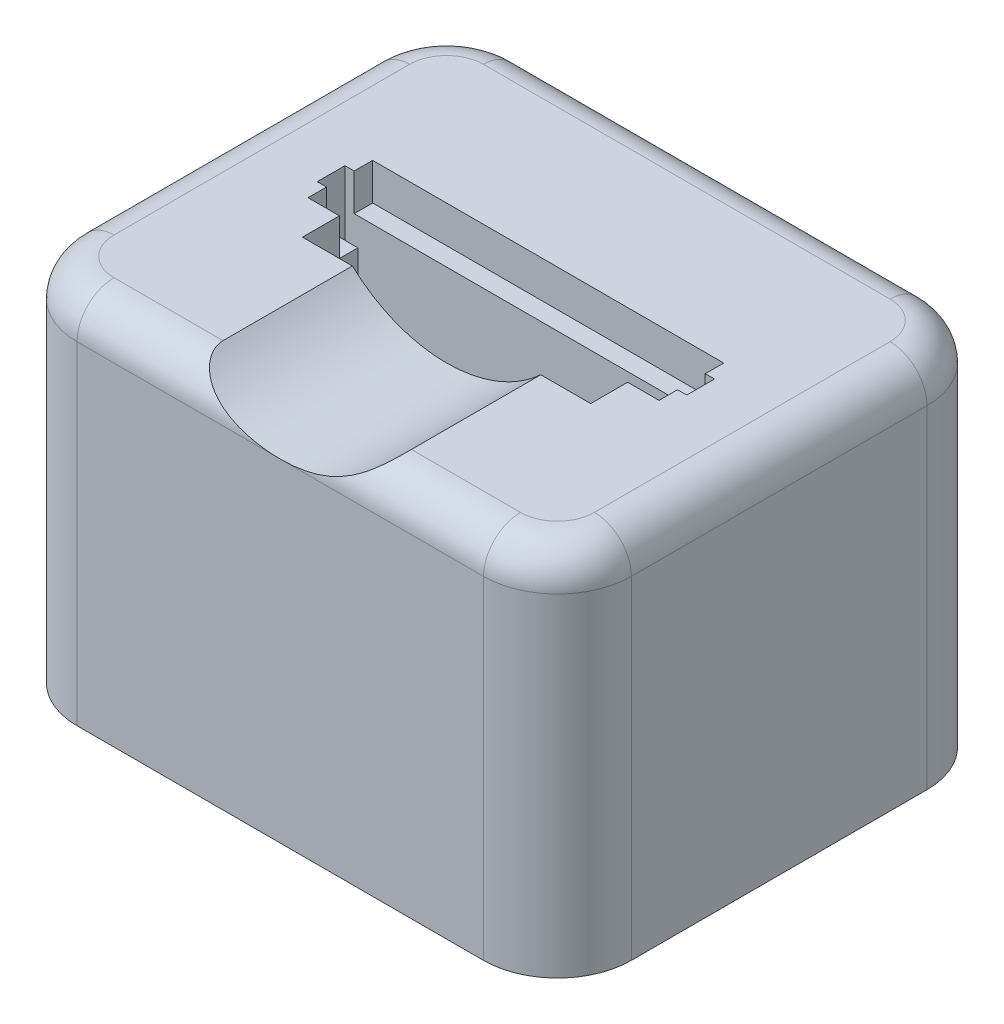
SolidWorks part; units mm, degrees
ref_plane "Спереди" through (0, 0, 0) normal (0, 0, 1) x (1, 0, 0)
ref_plane "Сверху" through (0, 0, 0) normal (0, 1, 0) x (1, 0, 0)
ref_plane "Справа" through (0, 0, 0) normal (1, 0, 0) x (0, 0, -1)
sketch "Эскиз1" plane through (0, 0, 0) normal (0, 1, 0) x (1, 0, 0)
  line L1 (4, 0) -> (26, 0)
  line L2 (0, 4) -> (0, 20)
  line L3 (4, 24) -> (26, 24)
  line L4 (30, 4) -> (30, 20)
  arc A0 (26, 24) -> (30, 20) centre (26, 20) cw
  arc A1 (26, 0) -> (30, 4) centre (26, 4) ccw
  arc A2 (4, 0) -> (0, 4) centre (4, 4) cw
  arc A3 (0, 20) -> (4, 24) centre (4, 20) cw
  point P10 (30, 0)
  point P13 (0, 0)
  point P16 (0, 24)
  dimension "D3" = 4
  dimension "D1" = 30
  dimension "D2" = 24
extrude "Бобышка-Вытянуть1" add sketch "Эскиз1" along normal blind 20
sketch "Эскиз2" plane through (0, 20, 0) normal (0, 1, 0) x (1, 0, 0)
  line L0 (0, 20) -> (0, 4) construction
  line L1 (5, 13.5) -> (25, 13.5)
  line L2 (5, 13.5) -> (5, 12)
  line L3 (5, 12) -> (25, 12)
  line L4 (25, 13.5) -> (25, 12)
  dimension "D1" = 1.5
  dimension "D2" = 20
  dimension "D3" = 5
  dimension "D4" = 12
sketch "Эскиз6" plane through (0, 0, 0) normal (0, -1, 0) x (1, 0, 0)
  circle A0 centre (4, -4) radius 0.9
  circle A1 centre (26, -4) radius 0.9
  circle A2 centre (26, -20) radius 0.9
  circle A3 centre (4, -20) radius 0.9
  dimension "D1" = 1.8
extrude "Вырез-Вытянуть5" cut sketch "Эскиз6" against normal blind 7
sketch "Эскиз3" plane through (0, 20, 0) normal (0, 1, 0) x (1, 0, 0)
  line L0 (5, 12) -> (25, 12) construction
  line L1 (7.2, 12) -> (22.8, 12)
  line L2 (7.2, 12) -> (7.2, 9)
  line L3 (7.2, 9) -> (22.8, 9)
  line L4 (22.8, 12) -> (22.8, 9)
  point P7 (15, 12)
  point P8 (15, 12)
  dimension "D1" = 15.6
  dimension "D2" = 3
extrude "Вырез-Вытянуть1" cut sketch "Эскиз3" against normal up to next
extrude "Вырез-Вытянуть2" cut sketch "Эскиз2" against normal offset from surface (9.5 mm away) 10.5 up to face at (15, 0, -10.5)
sketch "Эскиз4" plane through (0, 20, 0) normal (0, 1, 0) x (1, 0, 0)
  line L0 (5, 13.5) -> (5, 12) construction
  line L1 (5.5, 14.5) -> (24.5, 14.5)
  line L2 (5.5, 14.5) -> (5.5, 11)
  line L3 (5.5, 11) -> (24.5, 11)
  line L4 (24.5, 14.5) -> (24.5, 11)
  line L5 (25, 12) -> (25, 13.5) construction
  line L6 (25, 13.5) -> (5, 13.5) construction
  line L7 (5, 12) -> (7.2, 12) construction
  dimension "D1" = 0.5
  dimension "D2" = 0.5
  dimension "D3" = 1
  dimension "D4" = 1
extrude "Вырез-Вытянуть3" cut sketch "Эскиз4" against normal offset from surface (2 mm away) 18 up to face at (15, 0, -10.5)
sketch "Эскиз5" plane through (0, 0, 0) normal (0, 0, 1) x (1, 0, 0)
  line L0 (4, 20) -> (26, 20) construction
  circle A0 centre (15, 25.5) radius 7.5
  point P8 (15, 20)
  dimension "D1" = 15
  dimension "D2" = 25.5
extrude "Вырез-Вытянуть4" cut sketch "Эскиз5" against normal up to surface (9 mm away) up to face at (15, 10, -9)
fillet "Скругление1" radius 2 9 edges at (23.0495, 20, 0) (28.8284, 20, -1.1716) (6.9505, 20, 0) (1.1716, 20, -1.1716) (0, 20, -12) (1.1716, 20, -22.8284) (15, 20, -24) (28.8284, 20, -22.8284) (30, 20, -12)
